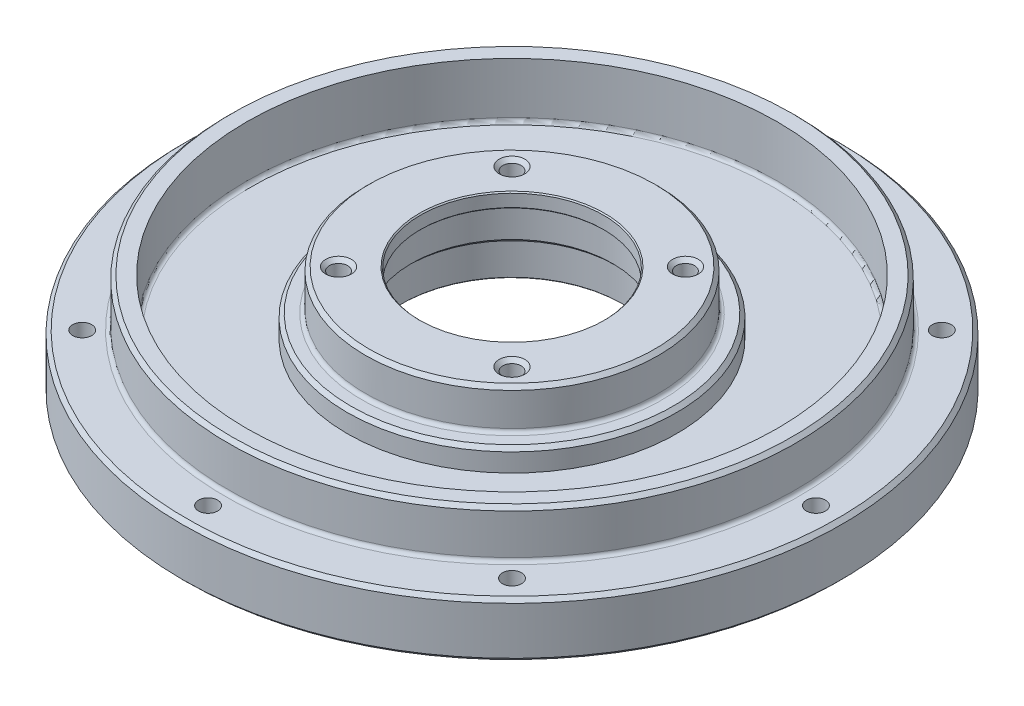
SolidWorks part; units mm, degrees
ref_plane "Front" through (0, 0, 0) normal (0, 0, 1) x (1, 0, 0)
ref_plane "Top" through (0, 0, 0) normal (0, 1, 0) x (1, 0, 0)
ref_plane "Right" through (0, 0, 0) normal (1, 0, 0) x (0, 0, -1)
sketch "Эскиз1" plane through (0, 0, 0) normal (0, 1, 0) x (1, 0, 0)
  circle A0 centre (0, 0) radius 90
  dimension "D1" = 180
extrude "Бобышка-Вытянуть1" add sketch "Эскиз1" along normal blind 30
sketch "Эскиз2" plane through (0, 0, 0) normal (1, 0, 0) x (0, 0, -1)
  line L0 (0, 0) -> (-38, 0)
  line L1 (-90, 0) -> (90, 0) construction
  line L2 (-38, 0) -> (-38, 6)
  line L3 (-38, 6) -> (-30, 6)
  line L4 (-30, 6) -> (-30, 16)
  line L5 (-30, 16) -> (-27.5, 16)
  line L6 (-27.5, 16) -> (-27.5, 26)
  line L7 (-27.5, 26) -> (-25, 26)
  line L8 (-25, 26) -> (-25, 67.4149)
  line L9 (-25, 67.4149) -> (0, 67.4149)
  line L10 (0, 67.4149) -> (0, 0)
  point P12 (-27.5, 21)
  dimension "D1" = 38
  dimension "D2" = 10
  dimension "D3" = 6
  dimension "D4" = 27.5
  dimension "D5" = 2.5
  dimension "D6" = 2.5
revolve "Вырез-Повернуть1" cut sketch "Эскиз2" angle 360 about L10 region at (0, 31.6141, 13.9011)
sketch "Эскиз3" plane through (0, 0, 0) normal (1, 0, 0) x (0, 0, -1)
  line L0 (0, 0) -> (0, 30)
  line L1 (90, 30) -> (-90, 30) construction
  line L2 (0, 30) -> (-40, 30)
  line L3 (-40, 30) -> (-40, 19)
  line L4 (-40, 19) -> (-45, 19)
  line L5 (-45, 19) -> (-45, 13)
  line L6 (-45, 13) -> (-72.5, 13)
  line L7 (-72.5, 13) -> (-72.5, 28)
  line L8 (-72.5, 28) -> (-77.5, 28)
  line L9 (-77.5, 28) -> (-77.5, 15)
  line L10 (-77.5, 15) -> (-112.6226, 15)
  line L11 (-112.6226, 15) -> (-112.6226, 53.5372)
  line L12 (-112.6226, 53.5372) -> (0, 53.5372)
  line L13 (0, 53.5372) -> (0, 30)
  dimension "D1" = 40
  dimension "D2" = 11
  dimension "D3" = 5
  dimension "D4" = 6
  dimension "D5" = 27.5
  dimension "D6" = 15
  dimension "D7" = 5
  dimension "D8" = 13
revolve "Вырез-Повернуть2" cut sketch "Эскиз3" angle 360 about L0 region at (0, 36.1881, 61.9667)
chamfer "Фаска1" distance 1 angle 45 2 edges at (0, 16, 27.5) (0, 19, -45)
chamfer "Фаска3" distance 1 angle 45 5 edges at (0, 0, 38) (0, 0, 90) (0, 30, -40) (0, 28, -77.5) (0, 15, -90)
chamfer "Фаска4" distance 0.3 angle 45 3 edges at (0, 30, 25) (0, 26, 25) (0, 6, 30)
fillet "Скругление1" radius 1 3 edges at (0, 19, -40) (0, 13, -72.5) (0, 15, -77.5)
sketch "Эскиз4" plane through (0, 0, 0) normal (0, 1, 0) x (1, 0, 0)
  line L0 (0, 0) -> (23.6881, 23.6881) construction
  line L1 (0, 0) -> (8.7592, 0) construction
  line L2 (25.3619, 22.0143) -> (25.9746, 24.3007)
  line L3 (25.9746, 24.3007) -> (24.3007, 25.9746)
  line L4 (24.3007, 25.9746) -> (22.0143, 25.3619)
  line L5 (22.0143, 25.3619) -> (21.4016, 23.0754)
  line L6 (21.4016, 23.0754) -> (23.0754, 21.4016)
  line L7 (23.0754, 21.4016) -> (25.3619, 22.0143)
  circle A0 centre (0, 0) radius 33.5 construction
  circle A1 centre (23.6881, 23.6881) radius 1.1
  circle A2 centre (23.6881, 23.6881) radius 2.5
  circle A3 centre (23.6881, 23.6881) radius 2.05 construction
  dimension "D1" = 67
  dimension "D2" = 5
  dimension "D3" = 2.2
  dimension "D5" = 4.1
  dimension "D4" = 45
extrude "Вырез-Вытянуть1" cut sketch "Эскиз4" along normal through all contours A1 region at (23.6881, 0, -23.6881)
extrude "Вырез-Вытянуть2" cut sketch "Эскиз4<3>" along normal through all from offset 11 contours A2
sketch "Эскиз4<3>" plane through (0, 0, 0) normal (0, 1, 0) x (1, 0, 0) same geometry as "Эскиз4"
extrude "Вырез-Вытянуть3" cut sketch "Эскиз4<4>" against normal blind 2 from offset 11 contours L6 L7 L2 L3 L4 L5 A1 region at (24.2019, 0, -21.7704)
sketch "Эскиз4<4>" plane through (0, 0, 0) normal (0, 1, 0) x (1, 0, 0) same geometry as "Эскиз4"
chamfer "Фаска5" distance 1 angle 45 1 edges at (23.6881, 30, -21.1881)
pattern_circular "Круговой массив1" count 4 over 360 about axis through (0, 0, 0) along (0, -1, 0) of "Фаска5", "Вырез-Вытянуть3", "Вырез-Вытянуть2", "Вырез-Вытянуть1"
sketch "Эскиз5" plane through (0, 0, 0) normal (0, 1, 0) x (1, 0, 0)
  line L0 (0, 0) -> (83, 0) construction
  line L1 (0, 0) -> (58.6899, -58.6899) construction
  line L2 (0, 0) -> (0, -83) construction
  line L3 (0, 0) -> (-58.6899, -58.6899) construction
  line L4 (0, 0) -> (-83, 0) construction
  line L5 (0, 0) -> (-58.6899, 58.6899) construction
  line L6 (0, 0) -> (0, 83) construction
  line L7 (0, 0) -> (58.6899, 58.6899) construction
  circle A0 centre (0, 0) radius 83 construction
  circle A1 centre (83, 0) radius 2.6
  circle A2 centre (58.6899, -58.6899) radius 2.6
  circle A3 centre (0, -83) radius 2.6
  circle A4 centre (-58.6899, -58.6899) radius 2.6
  circle A5 centre (-83, 0) radius 2.6
  circle A6 centre (-58.6899, 58.6899) radius 2.6
  circle A7 centre (0, 83) radius 2.6
  circle A8 centre (58.6899, 58.6899) radius 2.6
  point P22 (0, 0)
  dimension "D1" = 5.2
  dimension "D3" = 166
  dimension "D2" = 8
extrude "Вырез-Вытянуть4" cut sketch "Эскиз5" along normal through all
